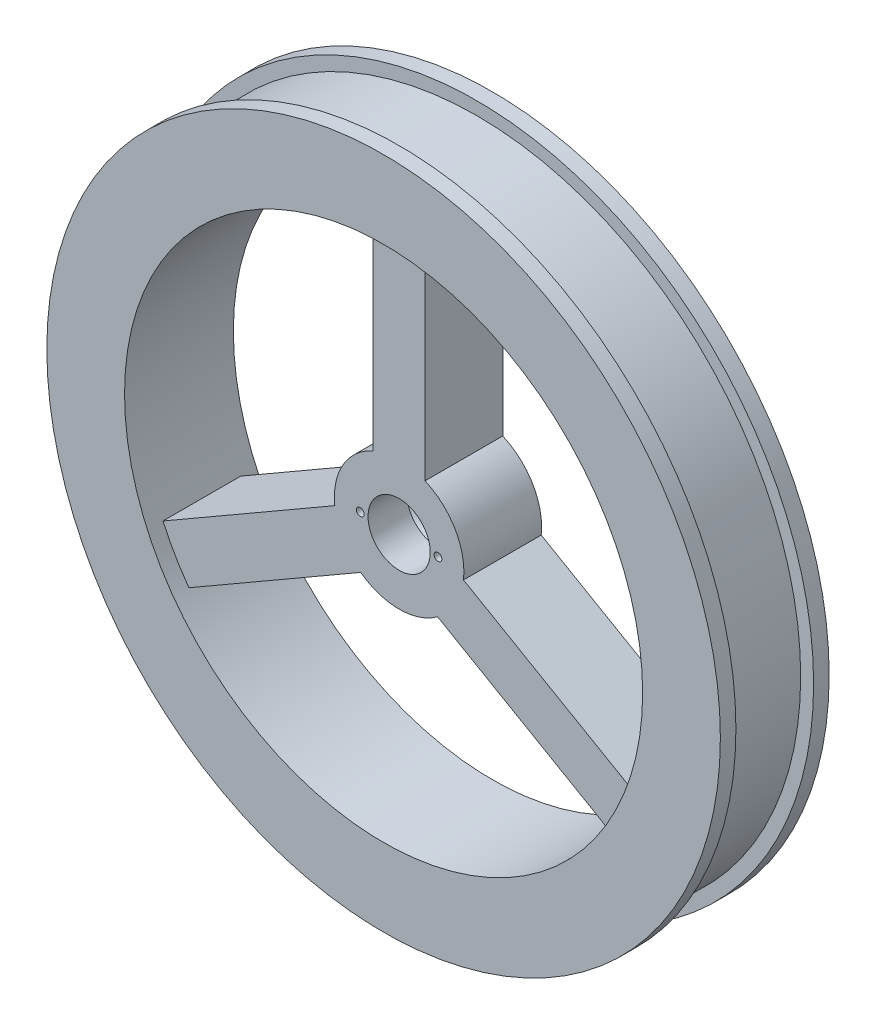
SolidWorks part; units mm, degrees
ref_plane "Front Plane" through (0, 0, 0) normal (0, 0, 1) x (1, 0, 0)
ref_plane "Top Plane" through (0, 0, 0) normal (0, 1, 0) x (1, 0, 0)
ref_plane "Right Plane" through (0, 0, 0) normal (1, 0, 0) x (0, 0, -1)
sketch "Sketch3" plane through (0, 0, 0) normal (0, 0, 1) x (1, 0, 0)
  line L0 (0, 0) -> (0, 489.8979) construction
  line L1 (-50, 497.4937) -> (-50, 114.5644)
  line L2 (50, 497.4937) -> (50, 114.5644)
  line L3 (0, 0) -> (-462.8145, -267.2061) construction
  line L4 (0, 0) -> (465.599, -268.8137) construction
  line L8 (124.2157, -13.9809) -> (455.8422, -205.4456)
  line L9 (-124.2157, -13.9809) -> (-455.8422, -205.4456)
  line L10 (-74.2157, -100.5835) -> (-405.8422, -292.0481)
  line L11 (74.2157, -100.5835) -> (405.8422, -292.0481)
  circle A0 centre (0, 0) radius 625
  arc A1 (-50, 497.4937) -> (-455.8422, -205.4456) centre (0, 0) ccw
  arc A2 (-50, 114.5644) -> (-124.2157, -13.9809) centre (0, 0) ccw
  arc A3 (124.2157, -13.9809) -> (50, 114.5644) centre (0, 0) ccw
  arc A4 (-74.2157, -100.5835) -> (74.2157, -100.5835) centre (0, 0) ccw
  arc A5 (-405.8422, -292.0481) -> (405.8422, -292.0481) centre (0, 0) ccw
  arc A6 (455.8422, -205.4456) -> (50, 497.4937) centre (0, 0) ccw
  point P7 (0, 0)
  dimension "D1" = 1250
  dimension "D2" = 1000
  dimension "D6" = 250
  dimension "D11" = 50
  dimension "D3" = 100
  dimension "D4" = 100
  dimension "D5" = 100
  dimension "D7" = 120
  dimension "D8" = 120
  dimension "D9" = 50
  dimension "D10" = 50
  dimension "D12" = 120
  dimension "D13" = 120
extrude "Boss-Extrude1" add sketch "Sketch3" along normal blind 150
sketch "Sketch4" plane through (0, 0, 0) normal (0, 0, -1) x (-1, 0, 0)
  circle A0 centre (0, 0) radius 60
  dimension "D1" = 120
extrude "Cut-Extrude1" cut sketch "Sketch4" against normal through all
ref_plane "Plane1" through (0, 0, 75) normal (0, 0, -1) x (-1, 0, 0)
sketch "Sketch5" plane through (0, 0, 75) normal (0, 0, -1) x (-1, 0, 0)
  circle A0 centre (0, 0) radius 55
  circle A1 centre (0, 0) radius 60
  dimension "D1" = 110
  dimension "D2" = 120
extrude "Boss-Extrude2" add sketch "Sketch5" along normal blind 32.5
fillet "Fillet3" radius 10 1 edges at (-55, 0, 75)
sketch "Sketch6" plane through (0, 0, 0) normal (0, 0, -1) x (-1, 0, 0)
  circle A0 centre (0, 0) radius 75 construction
  circle A1 centre (-75, 0) radius 7.5
  circle A2 centre (75, 0) radius 7.5
  dimension "D1" = 150
  dimension "D2" = 15
  dimension "D3" = 15
extrude "Cut-Extrude2" cut sketch "Sketch6" against normal blind 30
mirror "Mirror1" about plane through (0, 0, 75) normal (0, 0, -1) of "Cut-Extrude2"
sketch "Sketch7" plane through (0, 0, 0) normal (0, 0, -1) x (-1, 0, 0)
  circle A0 centre (0, 0) radius 500
  circle A1 centre (0, 0) radius 650
  dimension "D1" = 1000
  dimension "D2" = 1300
extrude "Boss-Extrude3" add sketch "Sketch7" along normal blind 30
mirror "Mirror2" about plane through (0, 0, 75) normal (0, 0, -1) of "Boss-Extrude3"
